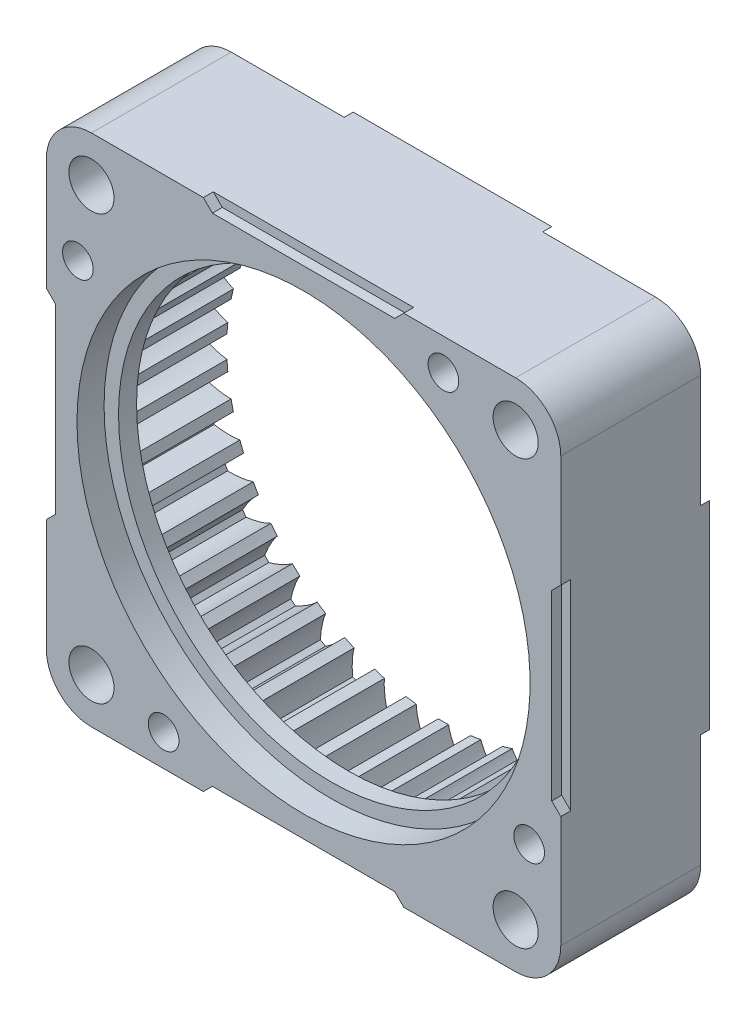
SolidWorks part; units mm, degrees
ref_plane "前视基准面" through (0, 0, 0) normal (0, 0, 1) x (1, 0, 0)
ref_plane "上视基准面" through (0, 0, 0) normal (0, 1, 0) x (1, 0, 0)
ref_plane "右视基准面" through (0, 0, 0) normal (1, 0, 0) x (0, 0, -1)
ref_axis "Axis1" through (0, 0, -88.99) along (0, 0, 1)
sketch "草图1" plane through (0, 0, 0) normal (0, 0, 1) x (1, 0, 0)
  circle A0 centre (0, 0) radius 26.7
  circle A1 centre (0, 0) radius 29.4
extrude "LaShenA" add sketch "草图1" along normal blind 10.5
sketch "SketchA" plane through (0, 0, 10.5) normal (0, 0, 1) x (1, 0, 0)
  arc A0 (0.568, 24) -> (-0.568, 24) centre (0, 0) ccw
  arc A1 (1.9411, 27.0887) -> (-1.9411, 27.0887) centre (0, 0) ccw
  circle A2 centre (0, 0) radius 23.6803 construction
  circle A3 centre (0, 0) radius 24 construction
  circle A4 centre (0, 0) radius 26.7 construction
  circle A5 centre (0, 0) radius 25.2 construction
  spline S0 degree 3 poles (0.568, 24) (0.5838, 24.0765) (0.6056, 24.1796) (0.6378, 24.3103) (0.6601, 24.3951) (0.6854, 24.4853) (0.7137, 24.5808) (0.7454, 24.6814) (0.7805, 24.7871) (0.8192, 24.8979) (0.8616, 25.0135) (0.9081, 25.134) (0.9586, 25.2592) (1.0134, 25.3891) (1.0727, 25.5235) (1.1365, 25.6623) (1.205, 25.8054) (1.2785, 25.9527) (1.357, 26.1041) (1.4407, 26.2594) (1.5297, 26.4185) (1.6241, 26.5814) (1.7596, 26.8066) (1.8668, 26.9755) (1.9411, 27.0887) knots 0 0 0 0 0.068895 0.092963 0.118769 0.146313 0.175597 0.206619 0.239379 0.273878 0.310116 0.348092 0.387807 0.429261 0.472453 0.517384 0.564054 0.612462 0.662609 0.714494 0.768118 0.82348 0.880582 1 1 1 1
  spline S1 degree 3 poles (-0.568, 24) (-0.5838, 24.0765) (-0.6056, 24.1796) (-0.6378, 24.3103) (-0.6601, 24.3951) (-0.6854, 24.4853) (-0.7137, 24.5808) (-0.7454, 24.6814) (-0.7805, 24.7871) (-0.8192, 24.8979) (-0.8616, 25.0135) (-0.9081, 25.134) (-0.9586, 25.2592) (-1.0134, 25.3891) (-1.0727, 25.5235) (-1.1365, 25.6623) (-1.205, 25.8054) (-1.2785, 25.9527) (-1.357, 26.1041) (-1.4407, 26.2594) (-1.5297, 26.4185) (-1.6241, 26.5814) (-1.7596, 26.8066) (-1.8668, 26.9755) (-1.9411, 27.0887) knots 0 0 0 0 0.068895 0.092963 0.118769 0.146313 0.175597 0.206619 0.239379 0.273878 0.310116 0.348092 0.387807 0.429261 0.472453 0.517384 0.564054 0.612462 0.662609 0.714494 0.768118 0.82348 0.880582 1 1 1 1
  dimension "Db" = 47.3605
  dimension "Da" = 48
  dimension "Df" = 53.4
  dimension "Dn" = 50.4
extrude "Cut-ExtrudeA" add sketch "SketchA" against normal blind 10.5
pattern_circular "www.KYTool.cn" count 42 over 360 about axis through (0, 0, -88.99) along (0, 0, 1) of "Cut-ExtrudeA"
sketch "草图11" plane through (0, 0, 0) normal (0, 1, 0) x (1, 0, 0)
  line L0 (0, 0) -> (0, -50000) construction
  line L1 (0, -10.5) -> (-23.5, -10.5) construction
  line L2 (-23.5, -10.5) -> (-29.4, -10.5)
  line L3 (-29.4, -10.5) -> (-29.4, -15.5)
  line L4 (-29.4, -15.5) -> (-25.1, -15.5)
  line L5 (-25.1, -15.5) -> (-25.1, -12.5)
  line L6 (-25.1, -12.5) -> (-23.5, -12.5)
  line L7 (-23.5, -12.5) -> (-23.5, -10.5)
  dimension "D1" = 47
  dimension "D2" = 50.2
  dimension "D3" = 58.8
  dimension "D4" = 10.5
  dimension "D5" = 15.5
  dimension "D6" = 3
revolve "旋转1" add sketch "草图11" angle 360 about L0
sketch "草图12" plane through (0, 0, 0) normal (0, 0, -1) x (-1, 0, 0)
  line L1 (-28.5, -28.5) -> (28.5, -28.5)
  line L2 (-28.5, -28.5) -> (-28.5, 28.5)
  line L3 (-28.5, 28.5) -> (28.5, 28.5)
  line L4 (28.5, -28.5) -> (28.5, 28.5)
  line L5 (-28.5, -28.5) -> (28.5, 28.5) construction
  line L6 (-28.5, 28.5) -> (28.5, -28.5) construction
  point P0 (0, 0)
  dimension "D1" = 57
extrude "切除-拉伸-薄壁2" cut sketch "草图12" against normal through all thin
sketch "草图13" plane through (0, 0, 0) normal (0, 0, -1) x (-1, 0, 0)
  line L0 (-28.5, 7.2187) -> (-28.5, 28.5)
  line L1 (-28.5, 28.5) -> (-7.2187, 28.5)
  arc A0 (-7.2187, 28.5) -> (-28.5, 7.2187) centre (0, 0) ccw construction
  arc A1 (-7.2187, 28.5) -> (-28.5, 7.2187) centre (0, 0) ccw
extrude "凸台-拉伸7" add sketch "草图13" against normal up to surface (15.5 mm away) up to face at (-25.1, 0, 15.5)
mirror "镜向1" about plane through (0, 0, 0) normal (0, 1, 0) of "凸台-拉伸7"
mirror "镜向2" about plane through (0, 0, 0) normal (1, 0, 0) of "镜向1", "凸台-拉伸7"
sketch "草图8" plane through (0, 0, 0) normal (0, 0, -1) x (-1, 0, 0)
  line L0 (-23.5, 23.5) -> (0, 0) construction
  line L1 (0, 0) -> (0, -50000) construction
  line L3 (28.5, 28.5) -> (-28.5, 28.5) construction
  circle A0 centre (-23.5, 23.5) radius 2.5
  circle A1 centre (-15.5, 25) radius 1.7
  dimension "D2" = 8
  dimension "D3" = 3.5
  dimension "D5" = 5
  dimension "D6" = 3.4
  dimension "D1" = 45
  dimension "D4" = 47
extrude "切除-拉伸1" cut sketch "草图8" against normal through all
sketch "草图9" plane through (0, 0, 0) normal (0, 0, -1) x (-1, 0, 0)
  line L0 (-28.5, 11) -> (-28.5, -11)
  line L2 (-28.5, -11) -> (-27.5, -10)
  line L3 (-27.5, -10) -> (-27.5, 10)
  line L4 (-27.5, 10) -> (-28.5, 11)
  line L5 (-27.5, 0) -> (0, 0) construction
  line L6 (-28.5, 28.5) -> (-28.5, -28.5) construction
  dimension "D1" = 135
  dimension "D2" = 135
  dimension "D3" = 1
  dimension "D4" = 22
extrude "凸台-拉伸6" add sketch "草图9" along normal blind 1
chamfer "倒角1" distance 0.2 angle 45 1 edges at (27.5, 0, -1)
sketch "草图10" plane through (0, 0, 15.5) normal (0, 0, 1) x (1, 0, 0)
  line L0 (28.5, 11.1) -> (28.5, -11.1)
  line L2 (28.5, -11.1) -> (27.5, -10.1)
  line L3 (27.5, -10.1) -> (27.5, 10.1)
  line L4 (27.5, 10.1) -> (28.5, 11.1)
  line L5 (0, 0) -> (27.5, 0) construction
  line L6 (28.5, -28.5) -> (28.5, 28.5) construction
  dimension "D1" = 135
  dimension "D2" = 135
  dimension "D3" = 22.2
  dimension "D4" = 1
extrude "切除-拉伸2" cut sketch "草图10" against normal blind 1.1
pattern_circular "阵列(圆周)1" count 4 over 360 about axis through (0, 0, 0) along (0, 0, 1) of "切除-拉伸1", "切除-拉伸2", "凸台-拉伸6", "倒角1"
fillet "圆角1" radius 5 4 edges at (28.5, 28.5, 7.75) (28.5, -28.5, 7.75) (-28.5, -28.5, 7.75) (-28.5, 28.5, 7.75)
